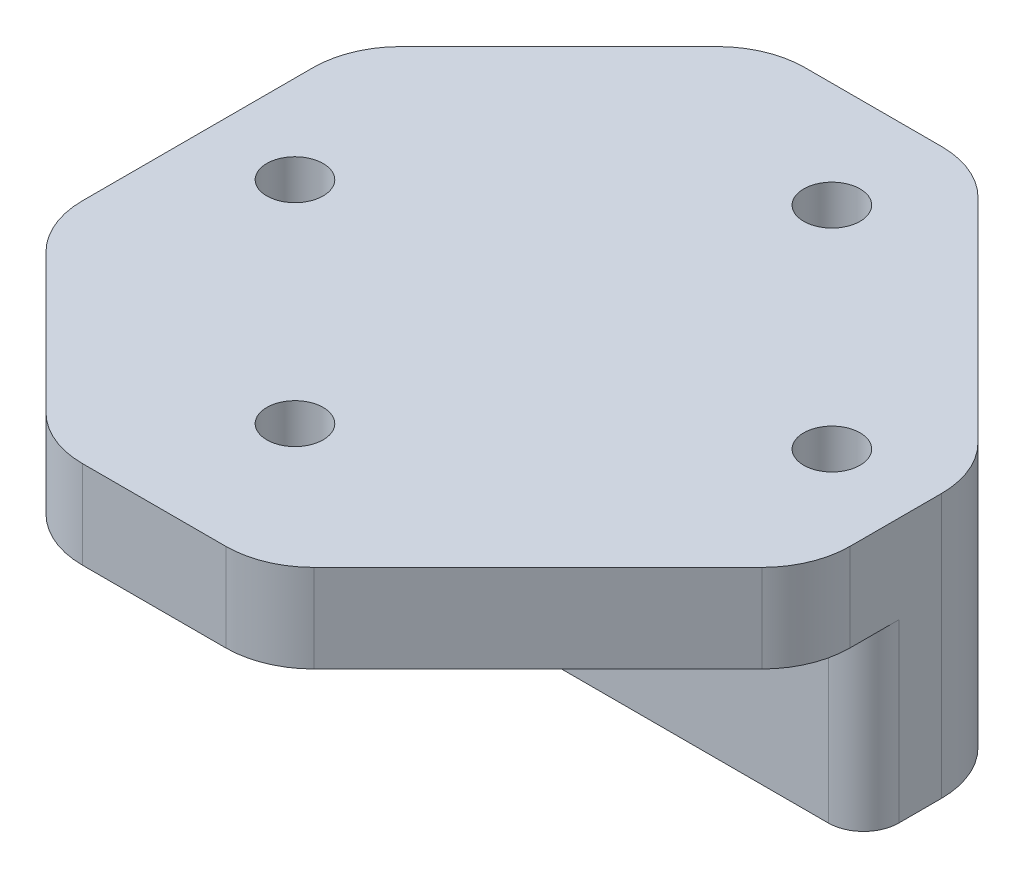
SolidWorks part; units mm, degrees
material "尼龙 101"
ref_plane "前视基准面" through (0, 0, 0) normal (0, 0, 1) x (1, 0, 0)
ref_plane "上视基准面" through (0, 0, 0) normal (0, 1, 0) x (1, 0, 0)
ref_plane "右视基准面" through (0, 0, 0) normal (1, 0, 0) x (0, 0, -1)
sketch "草图1" plane through (0, 0, 0) normal (0, 1, 0) x (1, 0, 0)
  line L0 (6.8, 32) -> (21.8, 17)
  line L1 (21.8, 17) -> (21.8, -8)
  line L2 (21.8, -8) -> (-17, -8)
  line L3 (-17, -8) -> (-17, 32)
  line L4 (-17, 32) -> (6.8, 32)
  circle A0 centre (0, 0) radius 1.6
  circle A1 centre (-12, 12) radius 1.6
  circle A2 centre (4.5, 26) radius 1.6
  circle A3 centre (16.5, 14) radius 1.6
  dimension "D1" = 12
  dimension "D2" = 3.2
  dimension "D3" = 12
  dimension "D4" = 16.5
  dimension "D5" = 14
  dimension "D6" = 12
  dimension "D7" = 12
  dimension "D10" = 5.3
  dimension "D9" = 5
  dimension "D8" = 135
  dimension "D11" = 8
  dimension "D12" = 25
  dimension "D13" = 40
extrude "凸台-拉伸1" add sketch "草图1" along normal blind 5
sketch "草图2" plane through (0, 0, 0) normal (0, -1, 0) x (1, 0, 0)
  line L0 (21.8, -10.5) -> (2, -10.5)
  line L1 (21.8, 8) -> (21.8, -17) construction
  line L2 (0, -12.5) -> (0, -32)
  line L3 (6.8, -32) -> (-17, -32) construction
  line L4 (0, -32) -> (6.8, -32)
  line L5 (6.8, -32) -> (21.8, -17)
  line L6 (21.8, -17) -> (21.8, -10.5)
  circle A0 centre (4.5, -26) radius 1.6 construction
  arc A2 (2, -10.5) -> (0, -12.5) centre (2, -12.5) ccw
  circle A3 centre (4.5, -26) radius 1.6
  circle A4 centre (16.5, -14) radius 1.6
  dimension "D1" = 15.5
  dimension "D2" = 2
  dimension "D3" = 3.2
  dimension "D4" = 3.2
extrude "凸台-拉伸2" add sketch "草图2" along normal blind 10
sketch "草图3" plane through (0, 5, 0) normal (0, 1, 0) x (1, 0, 0)
  line L0 (-5.1, 32) -> (-17, 20.1)
  line L1 (6.8, 32) -> (-17, 32) construction
  line L2 (-17, 32) -> (-17, -8) construction
  line L3 (-17, 20.1) -> (-17, 2.8579)
  line L4 (-17, 2.8579) -> (-6.1421, -8)
  line L5 (-17, -8) -> (21.8, -8) construction
  line L6 (-6.1421, -8) -> (6.1421, -8)
  line L7 (6.1421, -8) -> (21.8, 7.6579)
  line L8 (21.8, -8) -> (21.8, 17) construction
  line L9 (21.8, 7.6579) -> (21.8, 17)
  line L10 (21.8, 17) -> (6.8, 32) construction
  line L11 (21.8, 17) -> (6.8, 32)
  line L12 (6.8, 32) -> (-5.1, 32)
  circle A0 centre (0, 0) radius 1.6 construction
  dimension "D3" = 10
  dimension "D1" = 135
  dimension "D2" = 135
  dimension "D4" = 10
extrude "切除-拉伸1" cut sketch "草图3" against normal through all flip side to cut
fillet "圆角1" radius 5 8 edges at (21.8, 2.5, -7.6579) (6.1421, 2.5, 8) (-6.1421, 2.5, 8) (-17, 2.5, -2.8579) (-17, 2.5, -20.1) (-5.1, 2.5, -32) (21.8, -2.5, -17) (6.8, -2.5, -32)
fillet "圆角2" radius 2 2 edges at (0, -5, -32) (21.8, -5, -10.5)
sketch "草图4" plane through (-10.2, 0, -32) normal (0, 0, 1) x (1, 0, 0)
  line L1 (10.2, 0) -> (12.9, 0)
  line L2 (10.2, 0) -> (10.2, -5.5)
  line L3 (10.2, -5.5) -> (12.9, -5.5)
  line L4 (12.9, 0) -> (12.9, -5.5)
  line L5 (10.2, 0) -> (12.9, -5.5) construction
  line L6 (10.2, -5.5) -> (12.9, 0) construction
  point P4 (11.55, -2.75)
  dimension "D1" = 5.5
  dimension "D2" = 2.7
extrude "切除-拉伸2" cut sketch "草图4" along normal through all
